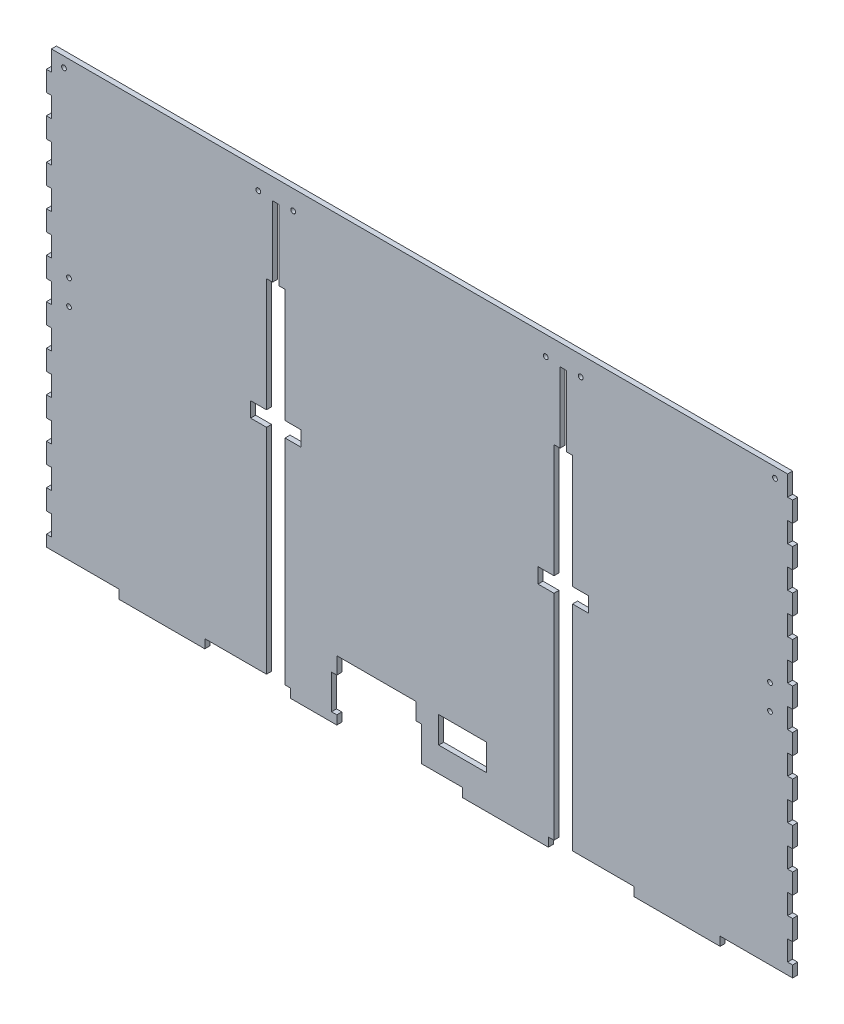
SolidWorks part; units mm, degrees
material "Acrylic (Medium-high impact)"
ref_plane "Front Plane" through (0, 0, 0) normal (0, 0, 1) x (1, 0, 0)
ref_plane "Top Plane" through (0, 0, 0) normal (0, 1, 0) x (1, 0, 0)
ref_plane "Right Plane" through (0, 0, 0) normal (1, 0, 0) x (0, 0, -1)
sketch "Sketch1" plane through (0, 0, 0) normal (0, 0, 1) x (1, 0, 0)
  line L0 (0, 139.7) -> (0, -139.7) construction
  line L1 (-406.4, 139.7) -> (406.4, 139.7)
  line L2 (-406.4, 139.7) -> (-406.4, -139.7)
  line L3 (-406.4, -139.7) -> (406.4, -139.7)
  line L4 (406.4, 139.7) -> (406.4, -139.7)
  line L49 (-381, 127) -> (-381, 114.3)
  line L54 (-381, 139.7) -> (-377.825, 139.7)
  line L55 (-381, 139.7) -> (-381, 127)
  line L56 (-381, 127) -> (-377.825, 127)
  line L57 (-377.825, 139.7) -> (-377.825, 127)
  line L58 (-381, 127) -> (-377.825, 127)
  line L59 (-377.825, 127) -> (-377.825, 114.3)
  line L60 (-381, 114.3) -> (-377.825, 114.3)
  line L61 (-381, 114.3) -> (-381, 101.6)
  line L62 (-381, 114.3) -> (-377.825, 114.3)
  line L63 (-377.825, 114.3) -> (-377.825, 101.6)
  line L64 (-381, 101.6) -> (-377.825, 101.6)
  line L65 (-381, 101.6) -> (-381, 88.9)
  line L66 (-381, 101.6) -> (-377.825, 101.6)
  line L67 (-377.825, 101.6) -> (-377.825, 88.9)
  line L68 (-381, 88.9) -> (-377.825, 88.9)
  line L69 (-381, 88.9) -> (-381, 76.2)
  line L70 (-381, 88.9) -> (-377.825, 88.9)
  line L71 (-377.825, 88.9) -> (-377.825, 76.2)
  line L72 (-381, 76.2) -> (-377.825, 76.2)
  line L73 (-381, 76.2) -> (-381, 63.5)
  line L74 (-381, 76.2) -> (-377.825, 76.2)
  line L75 (-377.825, 76.2) -> (-377.825, 63.5)
  line L76 (-381, 63.5) -> (-377.825, 63.5)
  line L77 (-381, 63.5) -> (-381, 50.8)
  line L78 (-381, 63.5) -> (-377.825, 63.5)
  line L79 (-377.825, 63.5) -> (-377.825, 50.8)
  line L80 (-381, 50.8) -> (-377.825, 50.8)
  line L81 (-381, 50.8) -> (-381, 38.1)
  line L82 (-381, 50.8) -> (-377.825, 50.8)
  line L83 (-377.825, 50.8) -> (-377.825, 38.1)
  line L84 (-381, 38.1) -> (-377.825, 38.1)
  line L85 (-381, 38.1) -> (-381, 25.4)
  line L86 (-381, 38.1) -> (-377.825, 38.1)
  line L87 (-377.825, 38.1) -> (-377.825, 25.4)
  line L88 (-381, 25.4) -> (-377.825, 25.4)
  line L89 (377.825, 127) -> (377.825, 114.3)
  line L90 (377.825, 139.7) -> (381, 139.7)
  line L91 (377.825, 139.7) -> (377.825, 127)
  line L92 (377.825, 127) -> (381, 127)
  line L93 (381, 139.7) -> (381, 127)
  line L94 (377.825, 127) -> (381, 127)
  line L95 (381, 127) -> (381, 114.3)
  line L96 (377.825, 114.3) -> (381, 114.3)
  line L97 (377.825, 114.3) -> (377.825, 101.6)
  line L98 (377.825, 114.3) -> (381, 114.3)
  line L99 (381, 114.3) -> (381, 101.6)
  line L100 (377.825, 101.6) -> (381, 101.6)
  line L101 (377.825, 101.6) -> (377.825, 88.9)
  line L102 (377.825, 101.6) -> (381, 101.6)
  line L103 (381, 101.6) -> (381, 88.9)
  line L104 (377.825, 88.9) -> (381, 88.9)
  line L105 (377.825, 88.9) -> (377.825, 76.2)
  line L106 (377.825, 88.9) -> (381, 88.9)
  line L107 (381, 88.9) -> (381, 76.2)
  line L108 (377.825, 76.2) -> (381, 76.2)
  line L109 (377.825, 76.2) -> (377.825, 63.5)
  line L110 (377.825, 76.2) -> (381, 76.2)
  line L111 (381, 76.2) -> (381, 63.5)
  line L112 (377.825, 63.5) -> (381, 63.5)
  line L113 (377.825, 63.5) -> (377.825, 50.8)
  line L114 (377.825, 63.5) -> (381, 63.5)
  line L115 (381, 63.5) -> (381, 50.8)
  line L116 (377.825, 50.8) -> (381, 50.8)
  line L117 (377.825, 50.8) -> (377.825, 38.1)
  line L118 (377.825, 50.8) -> (381, 50.8)
  line L119 (381, 50.8) -> (381, 38.1)
  line L120 (377.825, 38.1) -> (381, 38.1)
  line L121 (377.825, 38.1) -> (377.825, 25.4)
  line L122 (377.825, 38.1) -> (381, 38.1)
  line L123 (381, 38.1) -> (381, 25.4)
  line L124 (377.825, 25.4) -> (381, 25.4)
  line L125 (-352.2133, -134.112) -> (-352.2133, -139.7)
  line L126 (-406.4, -134.112) -> (-352.2133, -134.112)
  line L127 (-406.4, -134.112) -> (-406.4, -139.7)
  line L128 (-406.4, -139.7) -> (-352.2133, -139.7)
  line L129 (-352.2133, -134.112) -> (-352.2133, -139.7)
  line L130 (-352.2133, -134.112) -> (-298.0267, -134.112)
  line L131 (-298.0267, -134.112) -> (-298.0267, -139.7)
  line L132 (-352.2133, -139.7) -> (-298.0267, -139.7)
  line L133 (-298.0267, -134.112) -> (-298.0267, -139.7)
  line L134 (-298.0267, -134.112) -> (-243.84, -134.112)
  line L135 (-243.84, -134.112) -> (-243.84, -139.7)
  line L136 (-298.0267, -139.7) -> (-243.84, -139.7)
  line L137 (-243.84, -134.112) -> (-243.84, -139.7)
  line L138 (-243.84, -134.112) -> (-189.6533, -134.112)
  line L139 (-189.6533, -134.112) -> (-189.6533, -139.7)
  line L140 (-243.84, -139.7) -> (-189.6533, -139.7)
  line L141 (-189.6533, -134.112) -> (-189.6533, -139.7)
  line L142 (-189.6533, -134.112) -> (-135.4667, -134.112)
  line L143 (-135.4667, -134.112) -> (-135.4667, -139.7)
  line L144 (-189.6533, -139.7) -> (-135.4667, -139.7)
  line L145 (-135.4667, -134.112) -> (-135.4667, -139.7)
  line L146 (-135.4667, -134.112) -> (-81.28, -134.112)
  line L147 (-81.28, -134.112) -> (-81.28, -139.7)
  line L148 (-135.4667, -139.7) -> (-81.28, -139.7)
  line L149 (-81.28, -134.112) -> (-81.28, -139.7)
  line L150 (-81.28, -134.112) -> (-27.0933, -134.112)
  line L151 (-27.0933, -134.112) -> (-27.0933, -139.7)
  line L152 (-81.28, -139.7) -> (-27.0933, -139.7)
  line L153 (-27.0933, -134.112) -> (-27.0933, -139.7)
  line L154 (-27.0933, -134.112) -> (27.0933, -134.112)
  line L155 (27.0933, -134.112) -> (27.0933, -139.7)
  line L156 (-27.0933, -139.7) -> (27.0933, -139.7)
  line L157 (27.0933, -134.112) -> (27.0933, -139.7)
  line L158 (27.0933, -134.112) -> (81.28, -134.112)
  line L159 (81.28, -134.112) -> (81.28, -139.7)
  line L160 (27.0933, -139.7) -> (81.28, -139.7)
  line L161 (81.28, -134.112) -> (81.28, -139.7)
  line L162 (81.28, -134.112) -> (135.4667, -134.112)
  line L163 (135.4667, -134.112) -> (135.4667, -139.7)
  line L164 (81.28, -139.7) -> (135.4667, -139.7)
  line L165 (135.4667, -134.112) -> (135.4667, -139.7)
  line L166 (135.4667, -134.112) -> (189.6533, -134.112)
  line L167 (189.6533, -134.112) -> (189.6533, -139.7)
  line L168 (135.4667, -139.7) -> (189.6533, -139.7)
  line L169 (189.6533, -134.112) -> (189.6533, -139.7)
  line L170 (189.6533, -134.112) -> (243.84, -134.112)
  line L171 (243.84, -134.112) -> (243.84, -139.7)
  line L172 (189.6533, -139.7) -> (243.84, -139.7)
  line L173 (243.84, -134.112) -> (243.84, -139.7)
  line L174 (243.84, -134.112) -> (298.0267, -134.112)
  line L175 (298.0267, -134.112) -> (298.0267, -139.7)
  line L176 (243.84, -139.7) -> (298.0267, -139.7)
  line L177 (298.0267, -134.112) -> (298.0267, -139.7)
  line L178 (298.0267, -134.112) -> (352.2133, -134.112)
  line L179 (352.2133, -134.112) -> (352.2133, -139.7)
  line L180 (298.0267, -139.7) -> (352.2133, -139.7)
  line L181 (352.2133, -134.112) -> (352.2133, -139.7)
  line L182 (352.2133, -134.112) -> (406.4, -134.112)
  line L183 (406.4, -134.112) -> (406.4, -139.7)
  line L184 (352.2133, -139.7) -> (406.4, -139.7)
  line L205 (-90.678, 84.5227) -> (-90.678, -139.7) construction
  line L206 (90.678, 84.5227) -> (90.678, -139.7) construction
  line L207 (-90.678, -27.5886) -> (90.678, -27.5886) construction
  line L208 (-381, 25.4) -> (-381, 12.7)
  line L209 (-381, 25.4) -> (-377.825, 25.4)
  line L210 (-377.825, 25.4) -> (-377.825, 12.7)
  line L211 (-381, 12.7) -> (-377.825, 12.7)
  line L212 (-381, 12.7) -> (-381, 0)
  line L213 (-381, 12.7) -> (-377.825, 12.7)
  line L214 (-377.825, 12.7) -> (-377.825, 0)
  line L215 (-381, 0) -> (-377.825, 0)
  line L224 (-377.825, 0) -> (377.825, 0) construction
  line L229 (377.825, 25.4) -> (377.825, 12.7)
  line L230 (377.825, 25.4) -> (381, 25.4)
  line L231 (381, 25.4) -> (381, 12.7)
  line L232 (377.825, 12.7) -> (381, 12.7)
  line L233 (377.825, 12.7) -> (377.825, 0)
  line L234 (377.825, 12.7) -> (381, 12.7)
  line L235 (381, 12.7) -> (381, 0)
  line L236 (377.825, 0) -> (381, 0)
  line L237 (-381, 0) -> (-381, -12.7)
  line L238 (-381, 0) -> (-377.825, 0)
  line L239 (-377.825, 0) -> (-377.825, -12.7)
  line L240 (-381, -12.7) -> (-377.825, -12.7)
  line L241 (-381, -12.7) -> (-381, -25.4)
  line L242 (-381, -12.7) -> (-377.825, -12.7)
  line L243 (-377.825, -12.7) -> (-377.825, -25.4)
  line L244 (-381, -25.4) -> (-377.825, -25.4)
  line L245 (-381, -25.4) -> (-381, -38.1)
  line L246 (-381, -25.4) -> (-377.825, -25.4)
  line L247 (-377.825, -25.4) -> (-377.825, -38.1)
  line L248 (-381, -38.1) -> (-377.825, -38.1)
  line L249 (-381, -38.1) -> (-381, -50.8)
  line L250 (-381, -38.1) -> (-377.825, -38.1)
  line L251 (-377.825, -38.1) -> (-377.825, -50.8)
  line L252 (-381, -50.8) -> (-377.825, -50.8)
  line L253 (-381, -50.8) -> (-381, -63.5)
  line L254 (-381, -50.8) -> (-377.825, -50.8)
  line L255 (-377.825, -50.8) -> (-377.825, -63.5)
  line L256 (-381, -63.5) -> (-377.825, -63.5)
  line L257 (-381, -63.5) -> (-381, -76.2)
  line L258 (-381, -63.5) -> (-377.825, -63.5)
  line L259 (-377.825, -63.5) -> (-377.825, -76.2)
  line L260 (-381, -76.2) -> (-377.825, -76.2)
  line L261 (-381, -76.2) -> (-381, -88.9)
  line L262 (-381, -76.2) -> (-377.825, -76.2)
  line L263 (-377.825, -76.2) -> (-377.825, -88.9)
  line L264 (-381, -88.9) -> (-377.825, -88.9)
  line L265 (-381, -88.9) -> (-381, -101.6)
  line L266 (-381, -88.9) -> (-377.825, -88.9)
  line L267 (-377.825, -88.9) -> (-377.825, -101.6)
  line L268 (-381, -101.6) -> (-377.825, -101.6)
  line L269 (-381, -101.6) -> (-381, -114.3)
  line L270 (-381, -101.6) -> (-377.825, -101.6)
  line L271 (-377.825, -101.6) -> (-377.825, -114.3)
  line L272 (-381, -114.3) -> (-377.825, -114.3)
  line L273 (-381, -114.3) -> (-381, -127)
  line L274 (-381, -114.3) -> (-377.825, -114.3)
  line L275 (-377.825, -114.3) -> (-377.825, -127)
  line L276 (-381, -127) -> (-377.825, -127)
  line L277 (-381, -127) -> (-381, -139.7)
  line L278 (-381, -127) -> (-377.825, -127)
  line L279 (-377.825, -127) -> (-377.825, -139.7)
  line L280 (-381, -139.7) -> (-377.825, -139.7)
  line L281 (377.825, 0) -> (377.825, -12.7)
  line L282 (377.825, 0) -> (381, 0)
  line L283 (381, 0) -> (381, -12.7)
  line L284 (377.825, -12.7) -> (381, -12.7)
  line L285 (377.825, -12.7) -> (377.825, -25.4)
  line L286 (377.825, -12.7) -> (381, -12.7)
  line L287 (381, -12.7) -> (381, -25.4)
  line L288 (377.825, -25.4) -> (381, -25.4)
  line L289 (377.825, -25.4) -> (377.825, -38.1)
  line L290 (377.825, -25.4) -> (381, -25.4)
  line L291 (381, -25.4) -> (381, -38.1)
  line L292 (377.825, -38.1) -> (381, -38.1)
  line L293 (377.825, -38.1) -> (377.825, -50.8)
  line L294 (377.825, -38.1) -> (381, -38.1)
  line L295 (381, -38.1) -> (381, -50.8)
  line L296 (377.825, -50.8) -> (381, -50.8)
  line L297 (377.825, -50.8) -> (377.825, -63.5)
  line L298 (377.825, -50.8) -> (381, -50.8)
  line L299 (381, -50.8) -> (381, -63.5)
  line L300 (377.825, -63.5) -> (381, -63.5)
  line L301 (377.825, -63.5) -> (377.825, -76.2)
  line L302 (377.825, -63.5) -> (381, -63.5)
  line L303 (381, -63.5) -> (381, -76.2)
  line L304 (377.825, -76.2) -> (381, -76.2)
  line L305 (377.825, -76.2) -> (377.825, -88.9)
  line L306 (377.825, -76.2) -> (381, -76.2)
  line L307 (381, -76.2) -> (381, -88.9)
  line L308 (377.825, -88.9) -> (381, -88.9)
  line L309 (377.825, -88.9) -> (377.825, -101.6)
  line L310 (377.825, -88.9) -> (381, -88.9)
  line L311 (381, -88.9) -> (381, -101.6)
  line L312 (377.825, -101.6) -> (381, -101.6)
  line L313 (377.825, -101.6) -> (377.825, -114.3)
  line L314 (377.825, -101.6) -> (381, -101.6)
  line L315 (381, -101.6) -> (381, -114.3)
  line L316 (377.825, -114.3) -> (381, -114.3)
  line L317 (377.825, -114.3) -> (377.825, -127)
  line L318 (377.825, -114.3) -> (381, -114.3)
  line L319 (381, -114.3) -> (381, -127)
  line L320 (377.825, -127) -> (381, -127)
  line L321 (377.825, -127) -> (377.825, -139.7)
  line L322 (377.825, -127) -> (381, -127)
  line L323 (381, -127) -> (381, -139.7)
  line L324 (377.825, -139.7) -> (381, -139.7)
  point P6 (0, 0)
  point P128 (0, -27.5886)
  point P153 (0, 0)
  dimension "D4" = 12.7
  dimension "D5" = 3.175
  dimension "D10" = 181.356
  dimension "D12" = 755.65
  dimension "D8" = 812.8
  dimension "D11" = 54.1867
  dimension "D2" = 273.812
  dimension "D9" = 279.4
  dimension "D3" = 22
  dimension "D7" = 15
  dimension "D6" = 22
extrude "Main Extrude" add sketch "Sketch1" along normal blind 3.175 contours L321 L317 L313 L309 L305 L301 L297 L293 L289 L285 L281 L233 L229 L121 L117 L113 L109 L105 L101 L97 L89 L91 L1 L57 L59 L63 L67 L71 L75 L79 L83 L87 L210 L214 L239 L243 L247 L251 L255 L259 L263 L267 L271 L275 L279 L126 L130 L134 L138 L142 L146 | L277 L273 L269 L265 L261 L257 L253 L249 L245 L241 L237 L212 L208 L85 L81 L77 L73 L69 L65 L61 L49 L55 L1 L2 L126 | L319 L323 L182 L4 L1 L93 L95 L99 L103 L107 L111 L115 L119 L123 L231 L235 L283 L287 L291 L295 L299 L303 L307 L311 L315 | L126 L279 L3 L125 | L135 L134 L131 L3 | L143 L142 L139 L3 | L151 L150 L147 L3 | L159 L158 L155 L3 | L167 L166 L163 L3 | L175 L174 L171 L3 | L323 L182 L321 L184 | L89 L96 L95 L92 | L101 L104 L103 L100 | L109 L112 L111 L108 | L117 L120 L119 L116 | L229 L232 L231 L124 | L281 L284 L283 L236 | L289 L292 L291 L288 | L297 L300 L299 L296 | L305 L308 L307 L304 | L313 L316 L315 L312 | L323 L320 L321 L182 | L49 L60 L59 L56 | L65 L68 L67 L64 | L73 L76 L75 L72 | L81 L84 L83 L80 | L208 L211 L210 L88 | L237 L240 L239 L215 | L245 L248 L247 L244 | L253 L256 L255 L252 | L261 L264 L263 L260 | L269 L272 L271 L268 | L279 L276 L277 L126 | L277 L126 L2 L3 | L321 L182 L179 L3 | L182 L323 L3 L4 | L279 L126 L277 L128 region at (-393.7, 2.794, 0) region at (-393.7, -136.906, 0) region at (0, 2.794, 0) region at (-379.4125, 120.65, 0) region at (-379.4125, -130.556, 0) region at (-379.4125, -136.906, 0) region at (-365.0192, -136.906, 0) region at (393.7, 2.794, 0) region at (379.4125, 120.65, 0) region at (-379.4125, 95.25, 0) region at (-379.4125, -107.95, 0) region at (-270.9333, -136.906, 0) region at (393.7, -136.906, 0) region at (379.4125, 95.25, 0) region at (-379.4125, 69.85, 0) region at (-379.4125, -82.55, 0) region at (379.4125, -136.906, 0) region at (379.4125, -130.556, 0) region at (-162.56, -136.906, 0) region at (365.0192, -136.906, 0) region at (379.4125, 69.85, 0) region at (-379.4125, 44.45, 0) region at (-379.4125, -57.15, 0) region at (379.4125, -107.95, 0) region at (-54.1867, -136.906, 0) region at (270.9333, -136.906, 0) region at (379.4125, 44.45, 0) region at (-379.4125, 19.05, 0) region at (-379.4125, -31.75, 0) region at (379.4125, -82.55, 0) region at (54.1867, -136.906, 0) region at (162.56, -136.906, 0) region at (379.4125, 19.05, 0) region at (-379.4125, -6.35, 0) region at (379.4125, -57.15, 0) region at (379.4125, -6.35, 0) region at (379.4125, -31.75, 0)
sketch "Sketch8" plane through (0, 0, 3.175) normal (0, 0, 1) x (1, 0, 0)
  line L0 (-406.4, 139.7) -> (-406.4, -139.7) construction
  line L1 (-381, 28.2575) -> (-384.175, 28.2575)
  line L2 (-381, 28.2575) -> (-381, -3.6195)
  line L3 (-381, -3.6195) -> (-384.175, -3.6195)
  line L4 (-384.175, 28.2575) -> (-384.175, -3.6195)
  line L5 (-406.4, -139.7) -> (-352.2133, -139.7) construction
  line L6 (381, 28.2575) -> (384.175, 28.2575)
  line L7 (381, 28.2575) -> (381, -3.6195)
  line L8 (381, -3.6195) -> (384.175, -3.6195)
  line L9 (384.175, 28.2575) -> (384.175, -3.6195)
  line L11 (-381, 88.9) -> (-381, 76.2) construction
  line L12 (-352.2133, -134.112) -> (-298.0267, -134.112) construction
  line L13 (381, 88.9) -> (381, 76.2) construction
  line L14 (-393.7, -120.65) -> (393.7, -120.65) construction
  circle A0 centre (-393.7, -120.65) radius 1.5
  circle A1 centre (393.7, -120.65) radius 1.5
  point P6 (0, -120.65)
  point P16 (-384.175, 12.319)
  dimension "D5" = 3
  dimension "D1" = 31.877
  dimension "D2" = 3.175
  dimension "D3" = 146.431
  dimension "D4" = 19.05
  dimension "D6" = 12.7
extrude "Mount Holes" cut sketch "Sketch8" against normal through all
sketch "Sketch3" plane through (0, 0, 3.175) normal (0, 0, 1) x (1, 0, 0)
  line L0 (-135.4667, -134.112) -> (-81.28, -134.112) construction
  line L1 (-96.52, 126.492) -> (-84.836, 126.492)
  line L2 (-96.52, 126.492) -> (-96.52, -134.112)
  line L3 (-96.52, -134.112) -> (-84.836, -134.112)
  line L4 (-84.836, 126.492) -> (-84.836, -134.112)
  line L5 (81.28, -134.112) -> (135.4667, -134.112) construction
  line L6 (84.836, 126.492) -> (96.52, 126.492)
  line L7 (84.836, 126.492) -> (84.836, -134.112)
  line L8 (84.836, -134.112) -> (96.52, -134.112)
  line L9 (96.52, 126.492) -> (96.52, -134.112)
  line L10 (-84.836, -3.81) -> (84.836, -3.81) construction
  line L12 (-106.553, 10.3505) -> (-74.803, 10.3505)
  line L13 (-106.553, 10.3505) -> (-106.553, 0.8255)
  line L14 (-106.553, 0.8255) -> (-74.803, 0.8255)
  line L15 (-74.803, 10.3505) -> (-74.803, 0.8255)
  line L16 (74.803, 10.3505) -> (106.553, 10.3505)
  line L17 (74.803, 10.3505) -> (74.803, 0.8255)
  line L18 (74.803, 0.8255) -> (106.553, 0.8255)
  line L19 (106.553, 10.3505) -> (106.553, 0.8255)
  line L20 (-96.52, 126.492) -> (-92.6465, 126.492)
  line L21 (-96.52, 126.492) -> (-96.52, 82.042)
  line L22 (-96.52, 82.042) -> (-92.6465, 82.042)
  line L23 (-92.6465, 126.492) -> (-92.6465, 82.042)
  line L24 (-84.836, 126.492) -> (-88.7095, 126.492)
  line L25 (-84.836, 126.492) -> (-84.836, 82.042)
  line L26 (-84.836, 82.042) -> (-88.7095, 82.042)
  line L27 (-88.7095, 126.492) -> (-88.7095, 82.042)
  line L28 (84.836, 126.492) -> (88.7095, 126.492)
  line L29 (84.836, 126.492) -> (84.836, 82.042)
  line L30 (84.836, 82.042) -> (88.7095, 82.042)
  line L31 (88.7095, 126.492) -> (88.7095, 82.042)
  line L32 (96.52, 126.492) -> (92.6465, 126.492)
  line L33 (96.52, 126.492) -> (96.52, 82.042)
  line L34 (96.52, 82.042) -> (92.6465, 82.042)
  line L35 (92.6465, 126.492) -> (92.6465, 82.042)
  point P14 (-90.678, 126.492)
  point P15 (90.678, 126.492)
  point P16 (0, -3.81)
  point P27 (-90.678, 10.3505)
  point P28 (90.678, 10.3505)
  point P29 (-74.803, 5.588)
  dimension "D1" = 11.684
  dimension "D2" = 260.604
  dimension "D3" = 181.356
  dimension "D4" = 9.525
  dimension "D5" = 139.7
  dimension "D6" = 31.75
  dimension "D8" = 3.937
  dimension "D7" = 44.45
extrude "Door Slots" cut sketch "Sketch3" against normal through all contours L2 L12 L4 L1 | L2 L14 L4 L12 | L15 L12 L4 L14 | L13 L14 L2 L12 | L14 L2 L3 L4 | L7 L16 L9 L6 | L7 L18 L9 L16 | L19 L16 L9 L18 | L17 L18 L7 L16 | L18 L7 L8 L9 region at (-90.678, 56.2317, 3.175) region at (-90.678, 5.588, 3.175) region at (-101.5365, 5.588, 3.175) region at (-90.678, -66.6433, 3.175) region at (-79.8195, 5.588, 3.175) region at (90.678, 56.2317, 3.175) region at (90.678, 5.588, 3.175) region at (79.8195, 5.588, 3.175) region at (90.678, -66.6432, 3.175) region at (101.5365, 5.588, 3.175)
sketch "Sketch4" plane through (0, 0, 0) normal (0, 0, 1) x (1, 0, 0)
  line L1 (-81.28, -139.7) -> (-27.0933, -139.7) construction
  line L2 (-55.48, -112.41) -> (-52.178, -112.41)
  line L3 (-52.178, -112.41) -> (-52.178, -101.792)
  line L4 (-52.178, -101.792) -> (-2.178, -101.792)
  line L5 (-2.178, -101.792) -> (-2.178, -112.41)
  line L6 (-2.178, -112.41) -> (1.124, -112.41)
  line L9 (-55.48, -112.41) -> (-55.48, -134.112)
  line L10 (-55.48, -134.112) -> (-52.178, -134.112)
  line L11 (-52.178, -134.112) -> (-52.178, -139.7)
  line L12 (1.124, -112.41) -> (1.124, -134.112)
  line L13 (1.124, -134.112) -> (-2.178, -134.112)
  line L14 (-2.178, -134.112) -> (-2.178, -139.7)
  line L15 (-52.178, -139.7) -> (-2.178, -139.7)
  line L16 (-27.0933, -134.112) -> (27.0933, -134.112) construction
  line L18 (12.128, -101.792) -> (42.228, -101.792)
  line L19 (12.128, -101.792) -> (12.128, -118.491)
  line L20 (12.128, -118.491) -> (42.228, -118.491)
  line L21 (42.228, -101.792) -> (42.228, -118.491)
  line L22 (-27.0933, -134.112) -> (27.0933, -134.112) construction
  line L24 (-96.52, -134.112) -> (-84.836, -134.112) construction
  line L25 (84.836, -134.112) -> (96.52, -134.112) construction
  point P9 (-27.178, -101.792)
  point P10 (-27.178, -139.7)
  point P22 (27.178, -118.491)
  point P25 (90.678, -134.112)
  point P30 (-90.678, -134.112)
  dimension "D1" = 50
  dimension "D2" = 3.302
  dimension "D4" = 21.702
  dimension "D5" = 30.1
  dimension "D9" = 63.5
  dimension "D8" = 63.5
  dimension "D3" = 32.32
  dimension "D7" = 15.621
  dimension "D6" = 32.32
extrude "Trough and Lever Holes" cut sketch "Sketch4" along normal through all contours L11 L15 L14 L13 L12 L6 L5 L4 L3 L2 L9 L10 | L21 L18 L19 L20 region at (-27.178, -120.9228, 0) region at (27.178, -110.1415, 0)
sketch "Sketch5" plane through (0, 0, 3.175) normal (0, 0, 1) x (1, 0, 0)
  line L0 (-90.678, 126.492) -> (-90.678, -134.112) construction
  line L1 (-96.52, 126.492) -> (-84.836, 126.492) construction
  line L2 (-96.52, -134.112) -> (-84.836, -134.112) construction
  line L3 (90.678, 126.492) -> (90.678, -134.112) construction
  line L4 (84.836, 126.492) -> (96.52, 126.492) construction
  line L5 (84.836, -134.112) -> (96.52, -134.112) construction
  line L6 (-135.4667, -134.112) -> (-96.52, -134.112) construction
  line L19 (-99.998, -134.112) -> (-96.3199, -134.112)
  line L20 (-99.998, -134.112) -> (-99.998, -108.712)
  line L21 (-99.998, -108.712) -> (-96.3199, -108.712)
  line L22 (-96.3199, -134.112) -> (-96.3199, -108.712)
  line L24 (-99.998, -108.712) -> (-96.3199, -108.712)
  line L25 (-99.998, -108.712) -> (-99.998, -83.312)
  line L26 (-99.998, -83.312) -> (-96.3199, -83.312)
  line L27 (-96.3199, -108.712) -> (-96.3199, -83.312)
  line L28 (-96.3199, -83.312) -> (-99.998, -83.312)
  line L29 (-96.3199, -83.312) -> (-96.3199, -57.912)
  line L30 (-96.3199, -57.912) -> (-99.998, -57.912)
  line L31 (-99.998, -83.312) -> (-99.998, -57.912)
  line L32 (-99.998, -57.912) -> (-96.3199, -57.912)
  line L33 (-99.998, -57.912) -> (-99.998, -32.512)
  line L34 (-99.998, -32.512) -> (-96.3199, -32.512)
  line L35 (-96.3199, -57.912) -> (-96.3199, -32.512)
  line L36 (-96.3199, -32.512) -> (-99.998, -32.512)
  line L37 (-96.3199, -32.512) -> (-96.3199, -7.112)
  line L38 (-96.3199, -7.112) -> (-99.998, -7.112)
  line L39 (-99.998, -32.512) -> (-99.998, -7.112)
  line L40 (-81.358, -108.712) -> (-85.0361, -108.712)
  line L41 (-85.0361, -134.112) -> (-85.0361, -108.712)
  line L42 (-81.358, -134.112) -> (-85.0361, -134.112)
  line L43 (-81.358, -134.112) -> (-81.358, -108.712)
  line L44 (-81.358, -83.312) -> (-85.0361, -83.312)
  line L45 (-85.0361, -108.712) -> (-85.0361, -83.312)
  line L46 (-81.358, -108.712) -> (-85.0361, -108.712)
  line L47 (-81.358, -108.712) -> (-81.358, -83.312)
  line L48 (-85.0361, -57.912) -> (-81.358, -57.912)
  line L49 (-81.358, -83.312) -> (-81.358, -57.912)
  line L50 (-85.0361, -83.312) -> (-81.358, -83.312)
  line L51 (-85.0361, -83.312) -> (-85.0361, -57.912)
  line L52 (-81.358, -32.512) -> (-85.0361, -32.512)
  line L53 (-85.0361, -57.912) -> (-85.0361, -32.512)
  line L54 (-81.358, -57.912) -> (-85.0361, -57.912)
  line L55 (-81.358, -57.912) -> (-81.358, -32.512)
  line L56 (-85.0361, -7.112) -> (-81.358, -7.112)
  line L57 (-81.358, -32.512) -> (-81.358, -7.112)
  line L58 (-85.0361, -32.512) -> (-81.358, -32.512)
  line L59 (-85.0361, -32.512) -> (-85.0361, -7.112)
  line L60 (0, -1.7463) -> (0, 1.7463) construction
  line L61 (99.998, -108.712) -> (96.3199, -108.712)
  line L62 (96.3199, -134.112) -> (96.3199, -108.712)
  line L63 (99.998, -134.112) -> (96.3199, -134.112)
  line L64 (99.998, -134.112) -> (99.998, -108.712)
  line L65 (99.998, -83.312) -> (96.3199, -83.312)
  line L66 (96.3199, -108.712) -> (96.3199, -83.312)
  line L67 (99.998, -108.712) -> (96.3199, -108.712)
  line L68 (99.998, -108.712) -> (99.998, -83.312)
  line L69 (96.3199, -57.912) -> (99.998, -57.912)
  line L70 (99.998, -83.312) -> (99.998, -57.912)
  line L71 (96.3199, -83.312) -> (99.998, -83.312)
  line L72 (96.3199, -83.312) -> (96.3199, -57.912)
  line L73 (99.998, -32.512) -> (96.3199, -32.512)
  line L74 (96.3199, -57.912) -> (96.3199, -32.512)
  line L75 (99.998, -57.912) -> (96.3199, -57.912)
  line L76 (99.998, -57.912) -> (99.998, -32.512)
  line L77 (96.3199, -7.112) -> (99.998, -7.112)
  line L78 (99.998, -32.512) -> (99.998, -7.112)
  line L79 (96.3199, -32.512) -> (99.998, -32.512)
  line L80 (96.3199, -32.512) -> (96.3199, -7.112)
  line L81 (85.0361, -32.512) -> (85.0361, -7.112)
  line L82 (85.0361, -32.512) -> (81.358, -32.512)
  line L83 (81.358, -32.512) -> (81.358, -7.112)
  line L84 (85.0361, -7.112) -> (81.358, -7.112)
  line L85 (81.358, -57.912) -> (81.358, -32.512)
  line L86 (81.358, -57.912) -> (85.0361, -57.912)
  line L87 (85.0361, -57.912) -> (85.0361, -32.512)
  line L88 (81.358, -32.512) -> (85.0361, -32.512)
  line L89 (85.0361, -83.312) -> (85.0361, -57.912)
  line L90 (85.0361, -83.312) -> (81.358, -83.312)
  line L91 (81.358, -83.312) -> (81.358, -57.912)
  line L92 (85.0361, -57.912) -> (81.358, -57.912)
  line L93 (81.358, -108.712) -> (81.358, -83.312)
  line L94 (81.358, -108.712) -> (85.0361, -108.712)
  line L95 (85.0361, -108.712) -> (85.0361, -83.312)
  line L96 (81.358, -83.312) -> (85.0361, -83.312)
  line L97 (81.358, -134.112) -> (81.358, -108.712)
  line L98 (81.358, -134.112) -> (85.0361, -134.112)
  line L99 (85.0361, -134.112) -> (85.0361, -108.712)
  line L100 (81.358, -108.712) -> (85.0361, -108.712)
  dimension "D1" = 25.4
  dimension "D3" = 5.6419
  dimension "D2" = 9.32
extrude "Door Guide Slots" [suppressed] cut sketch "Sketch5" against normal through all contours L21 L27 L26 L25 | L30 L35 L34 L33 | L48 L55 L52 L53 | L40 L47 L44 L45 | L86 L87 L82 L85 | L94 L95 L90 L93 | L69 L76 L73 L74 | L61 L68 L65 L66
sketch "Sketch7" plane through (0, 0, 3.175) normal (0, 0, 1) x (1, 0, 0)
  line L0 (-25.908, -109.9715) -> (25.908, -109.9715) construction
  line L1 (-56.008, -105.601) -> (-25.908, -105.601)
  line L2 (-56.008, -105.601) -> (-56.008, -114.342)
  line L3 (-56.008, -114.342) -> (-25.908, -114.342)
  line L4 (-25.908, -105.601) -> (-25.908, -114.342)
  line L5 (56.008, -105.601) -> (25.908, -105.601)
  line L6 (56.008, -105.601) -> (56.008, -114.342)
  line L7 (56.008, -114.342) -> (25.908, -114.342)
  line L8 (25.908, -105.601) -> (25.908, -114.342)
  line L9 (0, -109.9715) -> (0, 0) construction
  line L10 (-135.4667, -134.112) -> (-96.52, -134.112) construction
  line L11 (1.124, -134.112) -> (27.0933, -134.112) construction
  dimension "D1" = 28.511
  dimension "D2" = 30.1
  dimension "D3" = 51.816
  dimension "D4" = 19.77
extrude "Lever Holes" [suppressed] cut sketch "Sketch7" against normal through all
sketch "Sketch10" plane through (0, 0, 3.175) normal (0, 0, 1) x (1, 0, 0)
  line L0 (-101.678, 127.492) -> (-79.678, 127.492) construction
  line L2 (-92.6465, 126.492) -> (-88.7095, 126.492) construction
  line L3 (-90.678, 127.492) -> (-90.678, 126.492) construction
  line L4 (79.678, 127.492) -> (101.678, 127.492) construction
  line L5 (90.678, 127.492) -> (90.678, 126.492) construction
  line L6 (88.7095, 126.492) -> (92.6465, 126.492) construction
  circle A0 centre (-101.678, 127.492) radius 1.5
  circle A1 centre (-79.678, 127.492) radius 1.5
  circle A2 centre (79.678, 127.492) radius 1.5
  circle A3 centre (101.678, 127.492) radius 1.5
  dimension "D1" = 3
  dimension "D2" = 22
  dimension "D3" = 1
extrude "Door Guide Mount Holes" cut sketch "Sketch10" against normal through all
sketch "Sketch12" plane through (0, 0, 3.175) normal (0, 0, 1) x (1, 0, 0)
  line L0 (-246.507, 20.193) -> (-246.507, 4.445) construction
  line L1 (-221.107, 20.193) -> (-221.107, 4.445) construction
  line L2 (-246.507, 20.193) -> (-221.107, 20.193) construction
  line L3 (-246.507, 4.445) -> (-221.107, 4.445) construction
  line L4 (-243.332, 133.35) -> (-224.282, 133.35) construction
  line L5 (-406.4, 139.7) -> (406.4, 139.7) construction
  line L6 (-233.807, 20.193) -> (-233.807, 133.35) construction
  line L7 (-243.84, -134.112) -> (-189.6533, -134.112) construction
  line L8 (0, -1.7463) -> (0, 1.7463) construction
  line L9 (233.807, 20.193) -> (233.807, 133.35) construction
  line L10 (243.332, 133.35) -> (224.282, 133.35) construction
  line L11 (246.507, 4.445) -> (221.107, 4.445) construction
  line L12 (246.507, 20.193) -> (221.107, 20.193) construction
  line L13 (221.107, 20.193) -> (221.107, 4.445) construction
  line L14 (246.507, 20.193) -> (246.507, 4.445) construction
  circle A0 centre (-246.507, 20.193) radius 1.5
  circle A1 centre (-246.507, 4.445) radius 1.5
  circle A2 centre (-221.107, 4.445) radius 1.5
  circle A3 centre (-221.107, 20.193) radius 1.5
  circle A4 centre (-243.332, 133.35) radius 1.5
  circle A5 centre (-224.282, 133.35) radius 1.5
  circle A6 centre (224.282, 133.35) radius 1.5
  circle A7 centre (243.332, 133.35) radius 1.5
  circle A8 centre (221.107, 20.193) radius 1.5
  circle A9 centre (221.107, 4.445) radius 1.5
  circle A10 centre (246.507, 4.445) radius 1.5
  circle A11 centre (246.507, 20.193) radius 1.5
  point P12 (-233.807, 133.35)
  dimension "D1" = 3
  dimension "D2" = 233.807
  dimension "D3" = 19.05
  dimension "D4" = 6.35
  dimension "D5" = 25.4
  dimension "D6" = 15.748
  dimension "D7" = 138.557
extrude "Extension Clip Holes" cut sketch "Sketch12" against normal through all
sketch "Sketch11" plane through (0, 0, 3.175) normal (0, 0, 1) x (1, 0, 0)
  line L0 (-232.2195, 139.7) -> (-232.2195, 127)
  line L1 (-232.2195, 127) -> (-235.3945, 127)
  line L2 (-235.3945, 127) -> (-235.3945, 114.3)
  line L3 (-235.3945, 114.3) -> (-232.2195, 114.3)
  line L4 (232.2195, 139.7) -> (232.2195, 127)
  line L5 (232.2195, 127) -> (235.3945, 127)
  line L6 (235.3945, 127) -> (235.3945, 114.3)
  line L7 (235.3945, 114.3) -> (232.2195, 114.3)
  line L9 (-381, 127) -> (-377.825, 127) construction
  line L10 (-377.825, 139.7) -> (-377.825, 127) construction
  line L11 (235.3945, 120.65) -> (-235.3945, 120.65) construction
  line L12 (-232.2195, 114.3) -> (-232.2195, 101.6)
  line L13 (-232.2195, 101.6) -> (-235.3945, 101.6)
  line L14 (-235.3945, 101.6) -> (-235.3945, 88.9)
  line L15 (-235.3945, 88.9) -> (-232.2195, 88.9)
  line L16 (232.2195, 114.3) -> (232.2195, 101.6)
  line L17 (232.2195, 101.6) -> (235.3945, 101.6)
  line L18 (235.3945, 101.6) -> (235.3945, 88.9)
  line L19 (235.3945, 88.9) -> (232.2195, 88.9)
  line L20 (-232.2195, 88.9) -> (-232.2195, 76.2)
  line L21 (-232.2195, 76.2) -> (-235.3945, 76.2)
  line L22 (-235.3945, 76.2) -> (-235.3945, 63.5)
  line L23 (-235.3945, 63.5) -> (-232.2195, 63.5)
  line L24 (232.2195, 88.9) -> (232.2195, 76.2)
  line L25 (232.2195, 76.2) -> (235.3945, 76.2)
  line L26 (235.3945, 76.2) -> (235.3945, 63.5)
  line L27 (235.3945, 63.5) -> (232.2195, 63.5)
  line L28 (-232.2195, 63.5) -> (-232.2195, 50.8)
  line L29 (-232.2195, 50.8) -> (-235.3945, 50.8)
  line L30 (-235.3945, 50.8) -> (-235.3945, 38.1)
  line L31 (-235.3945, 38.1) -> (-232.2195, 38.1)
  line L32 (232.2195, 63.5) -> (232.2195, 50.8)
  line L33 (232.2195, 50.8) -> (235.3945, 50.8)
  line L34 (235.3945, 50.8) -> (235.3945, 38.1)
  line L35 (235.3945, 38.1) -> (232.2195, 38.1)
  line L36 (-232.2195, 38.1) -> (-232.2195, 25.4)
  line L37 (-232.2195, 25.4) -> (-235.3945, 25.4)
  line L38 (-235.3945, 25.4) -> (-235.3945, 12.7)
  line L39 (-235.3945, 12.7) -> (-232.2195, 12.7)
  line L40 (232.2195, 38.1) -> (232.2195, 25.4)
  line L41 (232.2195, 25.4) -> (235.3945, 25.4)
  line L42 (235.3945, 25.4) -> (235.3945, 12.7)
  line L43 (235.3945, 12.7) -> (232.2195, 12.7)
  line L44 (-232.2195, 12.7) -> (-232.2195, 0)
  line L45 (-232.2195, 0) -> (-235.3945, 0)
  line L46 (-235.3945, 0) -> (-235.3945, -12.7)
  line L47 (-235.3945, -12.7) -> (-232.2195, -12.7)
  line L48 (232.2195, 12.7) -> (232.2195, 0)
  line L50 (232.2195, 0) -> (235.3945, 0)
  line L52 (235.3945, 0) -> (235.3945, -12.7)
  line L53 (235.3945, -12.7) -> (232.2195, -12.7)
  line L54 (-232.2195, -12.7) -> (-232.2195, -25.4)
  line L55 (-232.2195, -25.4) -> (-235.3945, -25.4)
  line L56 (-235.3945, -25.4) -> (-235.3945, -38.1)
  line L57 (-235.3945, -38.1) -> (-232.2195, -38.1)
  line L58 (232.2195, -12.7) -> (232.2195, -25.4)
  line L59 (232.2195, -25.4) -> (235.3945, -25.4)
  line L60 (235.3945, -25.4) -> (235.3945, -38.1)
  line L61 (235.3945, -38.1) -> (232.2195, -38.1)
  line L62 (-232.2195, -38.1) -> (-232.2195, -50.8)
  line L63 (-232.2195, -50.8) -> (-235.3945, -50.8)
  line L64 (-235.3945, -50.8) -> (-235.3945, -63.5)
  line L65 (-235.3945, -63.5) -> (-232.2195, -63.5)
  line L66 (232.2195, -38.1) -> (232.2195, -50.8)
  line L67 (232.2195, -50.8) -> (235.3945, -50.8)
  line L68 (235.3945, -50.8) -> (235.3945, -63.5)
  line L69 (235.3945, -63.5) -> (232.2195, -63.5)
  line L70 (-232.2195, -63.5) -> (-232.2195, -76.2)
  line L71 (-232.2195, -76.2) -> (-235.3945, -76.2)
  line L72 (-235.3945, -76.2) -> (-235.3945, -88.9)
  line L73 (-235.3945, -88.9) -> (-232.2195, -88.9)
  line L74 (232.2195, -63.5) -> (232.2195, -76.2)
  line L75 (232.2195, -76.2) -> (235.3945, -76.2)
  line L76 (235.3945, -76.2) -> (235.3945, -88.9)
  line L77 (235.3945, -88.9) -> (232.2195, -88.9)
  line L78 (-232.2195, -88.9) -> (-232.2195, -101.6)
  line L79 (-232.2195, -101.6) -> (-235.3945, -101.6)
  line L80 (-235.3945, -101.6) -> (-235.3945, -114.3)
  line L81 (-235.3945, -114.3) -> (-232.2195, -114.3)
  line L82 (232.2195, -88.9) -> (232.2195, -101.6)
  line L83 (232.2195, -101.6) -> (235.3945, -101.6)
  line L84 (235.3945, -101.6) -> (235.3945, -114.3)
  line L85 (235.3945, -114.3) -> (232.2195, -114.3)
  line L86 (-232.2195, -114.3) -> (-232.2195, -127)
  line L87 (-232.2195, -127) -> (-235.3945, -127)
  line L88 (-235.3945, -127) -> (-235.3945, -139.7)
  line L90 (232.2195, -114.3) -> (232.2195, -127)
  line L91 (232.2195, -127) -> (235.3945, -127)
  line L92 (235.3945, -127) -> (235.3945, -139.7)
  line L98 (-406.4, 139.7) -> (406.4, 139.7)
  line L99 (-406.4, 139.7) -> (-406.4, -139.7)
  line L100 (-406.4, -139.7) -> (406.4, -139.7)
  line L101 (406.4, 139.7) -> (406.4, -139.7)
  line L102 (-235.3945, -139.7) -> (-232.2195, -139.7)
  line L103 (235.3945, -139.7) -> (232.2195, -139.7)
  point P14 (-233.807, 127)
  point P15 (233.807, 114.3)
  point P18 (0, 120.65)
  dimension "D2" = 11
  dimension "D1" = 467.614
extrude "Extended Side Cut" [suppressed] cut sketch "Sketch11" against normal through all
extrude "Extension Center Cut" cut sketch "Sketch11<3>" against normal through all contours L99 L100 L39 L31 L23 L15 L2 L1 L98 | L101 L98 L80 L77 L76 L75 L72 L69 L68 L67 L64 L61 L60 L59 L56 L53 L52 L50 L100 region at (-320.0962, 0.0584, 3.175) region at (320.0962, 0.0584, 3.175)
sketch "Sketch11<3>" plane through (0, 0, 3.175) normal (0, 0, 1) x (1, 0, 0) same geometry as "Sketch11"
sketch "Sketch14" plane through (0, 0, 3.175) normal (0, 0, 1) x (1, 0, 0)
  line L1 (-232.2195, 139.7) -> (232.2195, 139.7)
  line L2 (-232.2195, 139.7) -> (-232.2195, 165.1)
  line L3 (-232.2195, 165.1) -> (232.2195, 165.1)
  line L4 (232.2195, 139.7) -> (232.2195, 165.1)
  dimension "D1" = 25.4
extrude "Extra Inch" [suppressed] add sketch "Sketch14" against normal up to surface (3.175 mm away) up to face at (27.178, -110.1415, 0)
sketch "Sketch15" [suppressed] plane through (0, 0, 3.175) normal (0, 0, 1) x (1, 0, 0)
  line L1 (-232.2195, 139.7) -> (232.2195, 139.7)
  line L2 (-232.2195, 139.7) -> (-232.2195, 165.1)
  line L3 (-232.2195, 165.1) -> (232.2195, 165.1)
  line L4 (232.2195, 139.7) -> (232.2195, 165.1)
  dimension "D1" = 25.4
extrude "Back Extra Inch" [suppressed] add sketch "Sketch15" against normal up to surface (3.175 mm away) up to face at (27.178, -110.1415, 0)
sketch "Sketch16" [suppressed] plane through (0, 0, 3.175) normal (0, 0, 1) x (1, 0, 0)
  line L1 (-232.2195, 139.7) -> (-406.4, 139.7)
  line L2 (-232.2195, 139.7) -> (-232.2195, 165.1)
  line L3 (-232.2195, 165.1) -> (-406.4, 165.1)
  line L4 (-406.4, 139.7) -> (-406.4, 165.1)
  dimension "D1" = 25.4
extrude "Extended Extra Inch" [suppressed] add sketch "Sketch16" against normal up to surface (3.175 mm away) up to face at (27.178, -110.1415, 0)
equation "\"bottomThickness\"= .220in"
equation "\"wallThickness\"= .125in"
equation "\"D4@Sketch1\"=\"D9@Sketch1\"/\"D3@Sketch1\""
equation "\"D5@Sketch1\"=\"wallThickness\""
equation "\"D1@Main Extrude\" = \"wallThickness\""
equation "\"D1@Sketch3\"=\"wallThickness\"*2+.19in+.02in"
equation "\"D2@Sketch4\"=\"wallThickness\"+.005in"
equation "\"D11@Sketch1\"=\"D8@Sketch1\"/\"D7@Sketch1\""
equation "\"D9@Sketch1\"=\"D2@Sketch1\"+\"bottomThickness\""
equation "\"D3@Sketch5\"=(\"wallThickness\"*2+.19in+.04)/2-(\"wallThickness\"-\"wallThickness\"/tan(80))*cos(80)"
equation "\"D8@Sketch3\"=\"wallThickness\"+.03in"
equation "\"D4@Sketch4\"=\"wallThickness\"+18.4mm+.005in"
equation "\"D2@Sketch5\"=(\"wallThickness\"*2+.19in+.04)/2+\"wallThickness\"/sin(80)"
